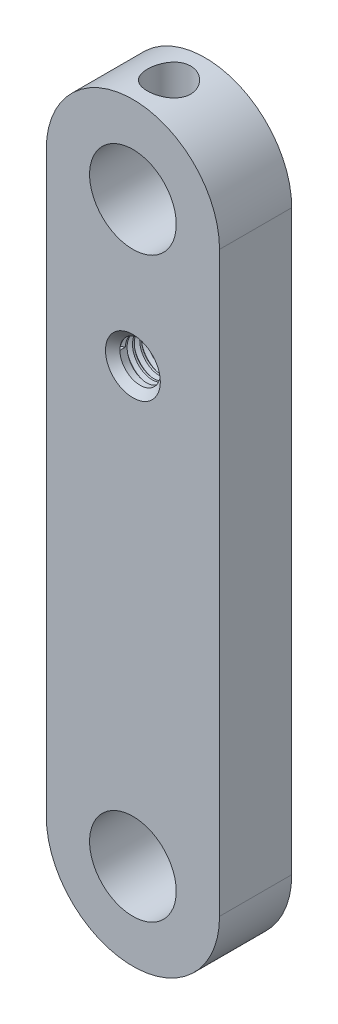
SolidWorks part; units mm, degrees
other "Uwaga1"
sketch "Szkic5" plane through (-6, 6, 0) normal (-0.3769, 0.9094, -0.176) x (0.7575, 0.412, 0.5065)
material "Stop 1060"
ref_plane "Płaszczyzna przednia" through (0, 0, 0) normal (0, 0, 1) x (1, 0, 0)
ref_plane "Płaszczyzna górna" through (0, 0, 0) normal (0, 1, 0) x (1, 0, 0)
ref_plane "Płaszczyzna prawa" through (0, 0, 0) normal (1, 0, 0) x (0, 0, -1)
sketch "Szkic1" plane through (0, 0, 0) normal (0, 0, 1) x (1, 0, 0)
  line L0 (0, 0) -> (0, -40)
  line L1 (6, -40) -> (6, 0)
  line L2 (-6, 0) -> (-6, -40)
  arc A1 (6, 0) -> (-6, 0) centre (0, 0) ccw
  circle A2 centre (0, -40) radius 3
  arc A3 (-6, -40) -> (6, -40) centre (0, -40) ccw
  circle A8 centre (0, -10) radius 1.4
  circle A9 centre (0, 0) radius 3
  dimension "D1" = 6
  dimension "D2" = 12
  dimension "D4" = 6
  dimension "D5" = 12
  dimension "D7" = 2.8
  dimension "D8" = 10
  dimension "D3" = 40
extrude "Dodanie-wyciągnięcie1" add sketch "Szkic1" along normal blind 5 contours L2 A3 L1 A1 A2 region at (0, -45.4663, 0)
chamfer "Sfazowanie1" distance 0.5 angle 45 2 edges at (1.4, -10, 0) (1.4, -10, 5)
thread "Gwint1" pitch 0.5 method cut profile "Profil gwintu1" start angle 0, offset 0, length 10, pitch 0.5, diameter 2.8
ref_plane "Płaszczyzna1" through (-1.4, -10, 4.5) normal (0, -1, 0) x (-1, 0, 0)
sketch "Profil gwintu1" plane through (-1.4, -10, 4.5) normal (0, -1, 0) x (-1, 0, 0)
  line L0 (0, 0) -> (0, 0.5) construction
  line L1 (0, 0) -> (0.2706, 0.1562)
  line L2 (0.2706, 0.1562) -> (0.2706, 0.2187)
  line L3 (0.2706, 0.2187) -> (0, 0.375)
  line L4 (0.2706, 0.1875) -> (0, 0.1875) construction
  line L11 (0, 0) -> (0, 0.375)
  point P2 (0, 0)
  dimension "Pitch" = 0.5
  dimension "Profile_Angle" = 60
  dimension "Profile_Land" = 0.0625
  dimension "Profile_Height" = 0.2706
ref_plane "Płaszczyzna2" through (0, 6, 0) normal (0, 1, 0) x (1, 0, 0)
sketch "Szkic4" plane through (0, 6, 0) normal (0, 1, 0) x (1, 0, 0)
  line L0 (6, -5) -> (6, 0) construction
  line L1 (6, 0) -> (-6, 0) construction
  circle A0 centre (0, -2.5) radius 1.5
  dimension "D1" = 6
  dimension "D2" = 2.5
  dimension "D3" = 3
extrude "Wytnij-wyciągnięcie1" cut sketch "Szkic4" against normal up to next
